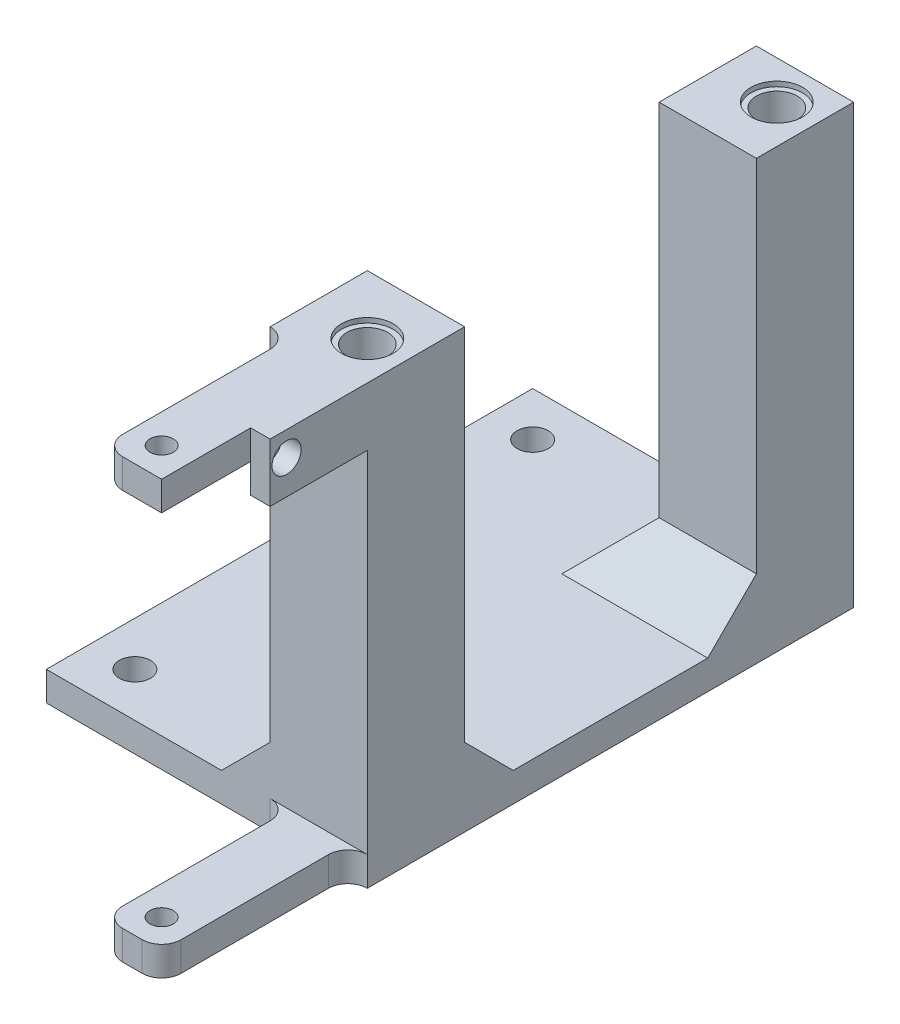
SolidWorks part; units mm, degrees
ref_plane "Front Plane" through (0, 0, 0) normal (0, 0, 1) x (1, 0, 0)
ref_plane "Top Plane" through (0, 0, 0) normal (0, 1, 0) x (1, 0, 0)
ref_plane "Right Plane" through (0, 0, 0) normal (1, 0, 0) x (0, 0, -1)
sketch "Sketch1" plane through (0, 0, 0) normal (0, 1, 0) x (1, 0, 0)
  line L1 (-6.5124, 9.686) -> (1.4876, 9.686)
  line L2 (-6.5124, 9.686) -> (-6.5124, -40.314)
  line L3 (-6.5124, -40.314) -> (1.4876, -40.314)
  line L4 (1.4876, 9.686) -> (1.4876, -40.314)
  line L5 (1.4876, 9.686) -> (26.4876, 9.686)
  line L6 (1.4876, 9.686) -> (1.4876, -40.314)
  line L7 (1.4876, -40.314) -> (26.4876, -40.314)
  line L8 (26.4876, 9.686) -> (26.4876, -40.314)
  circle A0 centre (-1.9624, -35.764) radius 1.6
  circle A1 centre (-1.9624, 5.136) radius 1.6
  dimension "D4" = 3.2
  dimension "D5" = 3.2
  dimension "D6" = 4.55
  dimension "D7" = 4.55
  dimension "D8" = 4.55
  dimension "D9" = 4.55
  dimension "D1" = 8
  dimension "D2" = 50
  dimension "D3" = 25
extrude "Boss-Extrude1" add sketch "Sketch1" along normal blind 3 contours A1 | A0 | L5 L8 L7 L3 L2 L1
sketch "Sketch2" plane through (0, 3, 0) normal (0, 1, 0) x (1, 0, 0)
  line L1 (26.4876, -40.314) -> (16.4876, -40.314)
  line L2 (26.4876, -40.314) -> (26.4876, -30.314)
  line L3 (26.4876, -30.314) -> (16.4876, -30.314)
  line L4 (16.4876, -40.314) -> (16.4876, -30.314)
  line L5 (26.4876, 9.686) -> (16.4876, 9.686)
  line L6 (26.4876, 9.686) -> (26.4876, -0.314)
  line L7 (26.4876, -0.314) -> (16.4876, -0.314)
  line L8 (16.4876, 9.686) -> (16.4876, -0.314)
  dimension "D1" = 10
  dimension "D2" = 10
  dimension "D3" = 10
  dimension "D4" = 10
extrude "Boss-Extrude2" add sketch "Sketch2" along normal blind 42
chamfer "Chamfer1" distance 5 angle 45 4 edges at (16.4876, 3, -4.686) (21.4876, 3, 0.314) (16.4876, 3, 35.314) (21.4876, 3, 30.314)
ref_plane "Plane1" through (0, 45, 0) normal (0, 1, 0) x (1, 0, 0)
sketch "Sketch3" plane through (0, 45, 0) normal (0, 1, 0) x (1, 0, 0)
  line L0 (26.4876, -40.314) -> (26.4876, -30.314) construction
  line L1 (16.4876, -40.314) -> (26.4876, -40.314) construction
  line L2 (26.4876, -0.314) -> (26.4876, 9.686) construction
  line L3 (26.4876, 9.686) -> (16.4876, 9.686) construction
  circle A0 centre (22.5376, -36.364) radius 2.1
  circle A1 centre (22.5376, 5.736) radius 2.1
  dimension "D1" = 4.2
  dimension "D3" = 3.95
  dimension "D4" = 4.2
  dimension "D6" = 3.95
  dimension "D2" = 3.95
  dimension "D5" = 3.95
extrude "Cut-Extrude1" cut sketch "Sketch3" against normal blind 52
sketch "Sketch4" plane through (0, 45, 0) normal (0, 1, 0) x (1, 0, 0)
  circle A0 centre (22.5376, -36.364) radius 2.65
  circle A1 centre (22.5376, 5.736) radius 2.65
  dimension "D1" = 5.3
  dimension "D2" = 5.3
extrude "Cut-Extrude2" cut sketch "Sketch4" against normal blind 0.5
ref_plane "Plane2" through (0, 22.5, 0) normal (0, -1, 0) x (-1, 0, 0)
mirror "Mirror1" about plane through (0, 22.5, 0) normal (0, -1, 0) of "Cut-Extrude2"
sketch "Sketch5" plane through (0, 0, -9.686) normal (0, 0, -1) x (-1, 0, 0)
  line L0 (-22.4876, 36.5) -> (-17.9876, 36.5) construction
  line L1 (-18.2876, 36.2) -> (-22.2399, 36.2)
  line L2 (-18.2876, 36.2) -> (-18.2876, 31.6868)
  line L3 (-18.2876, 31.6868) -> (-22.2399, 31.6868)
  line L4 (-22.2399, 36.2) -> (-22.2399, 31.6868)
  line L5 (-17.9876, 32.25) -> (-17.9876, 37) construction
  dimension "D1" = 0.3
  dimension "D2" = 0.3
sketch "Sketch11" plane through (0, 0, 40.314) normal (0, 0, 1) x (1, 0, 0)
  line L0 (16.4876, 45) -> (26.4876, 45) construction
  line L1 (18.4876, 45) -> (24.4876, 45)
  line L2 (18.4876, 45) -> (18.4876, 42)
  line L3 (18.4876, 42) -> (24.4876, 42)
  line L4 (24.4876, 45) -> (24.4876, 42)
  line L5 (-6.5124, 0) -> (26.4876, 0) construction
  line L6 (18.4876, 0) -> (24.4876, 0)
  line L7 (18.4876, 0) -> (18.4876, 3)
  line L8 (18.4876, 3) -> (24.4876, 3)
  line L9 (24.4876, 0) -> (24.4876, 3)
  line L10 (21.4876, 8) -> (21.4876, 0) construction
  line L11 (21.4876, 8) -> (21.4876, 45) construction
  line L13 (-6.5124, 3) -> (11.4876, 3) construction
  line L14 (16.4876, 8) -> (26.4876, 8) construction
  line L15 (26.4876, 8) -> (39.3241, 4.4212) construction
  line L16 (39.3241, 4.4212) -> (39.5028, 4.4212) construction
  dimension "D1" = 3
  dimension "D2" = 3
  dimension "D3" = 3
  dimension "D4" = 3
  dimension "D5" = 3
extrude "Boss-Extrude7" add sketch "Sketch11" along normal up to surface (19.15 mm away)
sketch "Sketch12" plane through (0, 0, 0) normal (0, -1, 0) x (1, 0, 0)
  line L0 (24.4876, 59.464) -> (24.4876, 40.314) construction
  line L1 (18.4876, 59.464) -> (24.4876, 59.464) construction
  line L2 (18.4876, 59.464) -> (18.4876, 53.464) construction
  line L3 (18.4876, 53.464) -> (24.4876, 53.464) construction
  line L4 (24.4876, 59.464) -> (24.4876, 53.464) construction
  line L5 (18.4876, 59.464) -> (24.4876, 53.464) construction
  line L6 (18.4876, 53.464) -> (24.4876, 59.464) construction
  circle A0 centre (21.4876, 56.464) radius 1.2
  point P494 (21.4876, 56.464)
  dimension "D1" = 2.4
  dimension "D2" = 6
extrude "Cut-Extrude5" cut sketch "Sketch12" against normal through all
fillet "Fillet1" radius 2 6 edges at (18.4876, 43.5, 40.314) (18.4876, 43.5, 59.464) (24.4876, 1.5, 59.464) (18.4876, 1.5, 59.464) (18.4876, 1.5, 40.314) (24.4876, 1.5, 40.314)
sketch "Sketch13" plane through (0, 0, 40.314) normal (0, 0, 1) x (1, 0, 0)
  line L0 (26.4876, 45) -> (26.4876, 3) construction
  line L1 (24.4876, 45) -> (26.4876, 45)
  line L2 (24.4876, 45) -> (24.4876, 42)
  line L3 (24.4876, 42) -> (26.4876, 42)
  line L4 (26.4876, 45) -> (26.4876, 42)
  line L5 (16.4876, 42) -> (24.4876, 42) construction
extrude "Boss-Extrude8" add sketch "Sketch13" along normal blind 10
sketch "Sketch14" plane through (0, 42, 0) normal (0, -1, 0) x (1, 0, 0)
  line L0 (16.4876, 40.314) -> (26.4876, 40.314) construction
  line L1 (26.4876, 50.314) -> (24.4876, 50.314)
  line L2 (26.4876, 50.314) -> (26.4876, 40.314)
  line L3 (26.4876, 40.314) -> (24.4876, 40.314)
  line L4 (24.4876, 50.314) -> (24.4876, 40.314)
extrude "Boss-Extrude9" add sketch "Sketch14" along normal blind 3
sketch "Sketch15" plane through (26.4876, 0, 0) normal (1, 0, 0) x (0, 0, -1)
  circle A0 centre (-48.614, 42.5) radius 1.5
  dimension "D1" = 3
extrude "Cut-Extrude6" cut sketch "Sketch15" against normal blind 3
